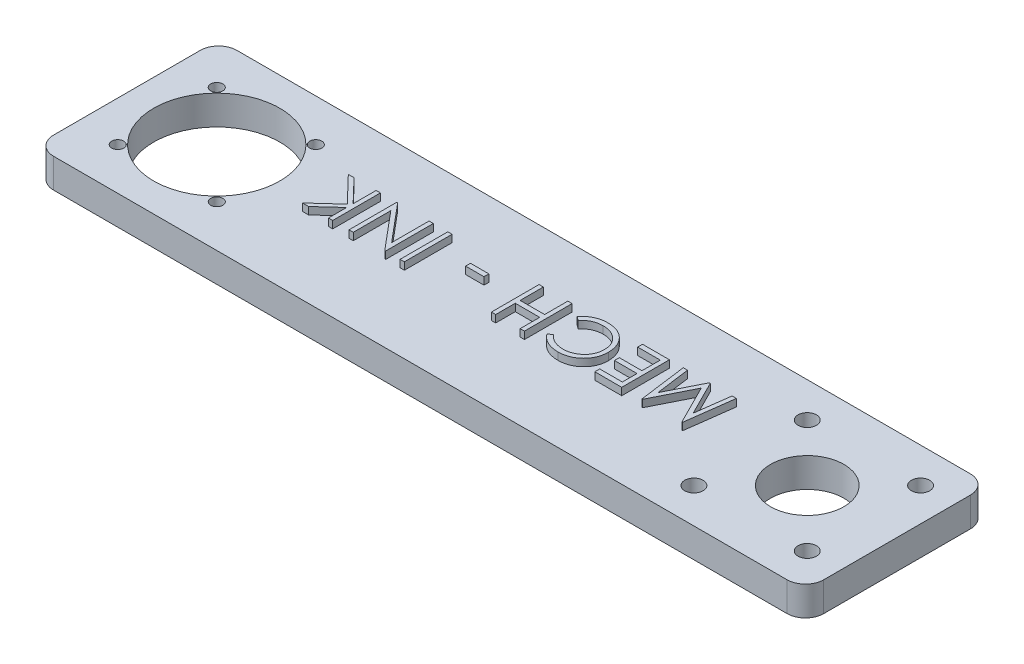
SolidWorks part; units mm, degrees
ref_plane "Front Plane" through (0, 0, 0) normal (0, 0, 1) x (1, 0, 0)
ref_plane "Top Plane" through (0, 0, 0) normal (0, 1, 0) x (1, 0, 0)
ref_plane "Right Plane" through (0, 0, 0) normal (1, 0, 0) x (0, 0, -1)
sketch "Croquis1" plane through (0, 0, 0) normal (0, 1, 0) x (1, 0, 0)
  line L1 (-105, 25) -> (105, 25)
  line L2 (-105, 25) -> (-105, -25)
  line L3 (-105, -25) -> (105, -25)
  line L4 (105, 25) -> (105, -25)
  line L5 (-105, 25) -> (105, -25) construction
  line L6 (-105, -25) -> (105, 25) construction
  circle A0 centre (-80.5, 0) radius 17.2
  circle A1 centre (80.5, 0) radius 10
  circle A2 centre (95.95, -15.45) radius 2.5
  circle A3 centre (95.95, 15.45) radius 2.5
  circle A4 centre (65.05, 15.45) radius 2.5
  circle A5 centre (65.05, -15.45) radius 2.5
  circle A6 centre (-94, -13.5) radius 1.65
  circle A7 centre (-67, -13.5) radius 1.65
  circle A8 centre (-67, 13.5) radius 1.65
  circle A9 centre (-94, 13.5) radius 1.65
  point P0 (0, 0)
  dimension "D4" = 34.4
  dimension "D6" = 5
  dimension "D7" = 20
  dimension "D1" = 210
  dimension "D2" = 50
  dimension "D3" = 161
  dimension "D5" = 24.5
extrude "Saliente-Extruir1" add sketch "Croquis1" along normal blind 8
extrude "Saliente-Extruir2" add sketch "Croquis1<3>" along normal blind 8
sketch "Croquis1<3>" plane through (0, 0, 0) normal (0, 1, 0) x (1, 0, 0) same geometry as "Croquis1"
extrude "Saliente-Extruir3" add sketch "Croquis1<4>" along normal blind 6 contours L4 L1 L2 L3 A1 A0 region at (5.0263, 0, 0)
sketch "Croquis1<4>" plane through (0, 0, 0) normal (0, 1, 0) x (1, 0, 0) same geometry as "Croquis1"
sketch "Croquis2" plane through (0, 8, 0) normal (0, 1, 0) x (1, 0, 0)
  line L0 (-57.664, 8.9051) -> (57.664, 8.9051) construction
  text T0 "MECH - INK" font "Century Gothic" height 13
  point P4 (0, 0)
extrude "Saliente-Extruir4" add sketch "Croquis2" along normal blind 2
fillet "Redondeo1" radius 5 4 edges at (105, 4, -25) (105, 4, 25) (-105, 4, 25) (-105, 4, -25)
